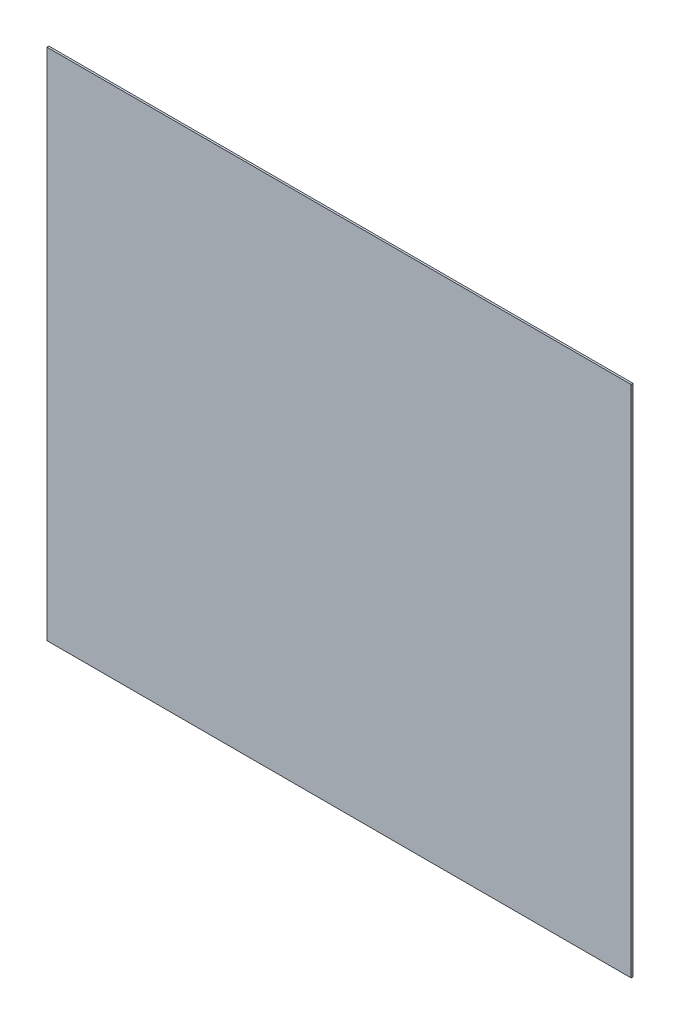
SolidWorks part; units mm, degrees
ref_plane "Front Plane" through (0, 0, 0) normal (0, 0, 1) x (1, 0, 0)
ref_plane "Top Plane" through (0, 0, 0) normal (0, 1, 0) x (1, 0, 0)
ref_plane "Right Plane" through (0, 0, 0) normal (1, 0, 0) x (0, 0, -1)
sketch "Sketch1" plane through (0, 0, 0) normal (0, 0, 1) x (1, 0, 0)
  line L1 (0, 0) -> (762, 0)
  line L2 (0, 0) -> (0, 670.269)
  line L3 (0, 670.269) -> (762, 670.269)
  line L4 (762, 0) -> (762, 670.269)
  dimension "D1" = 670.269
  dimension "D2" = 762
extrude "Boss-Extrude1" add sketch "Sketch1" along normal blind 2.54
